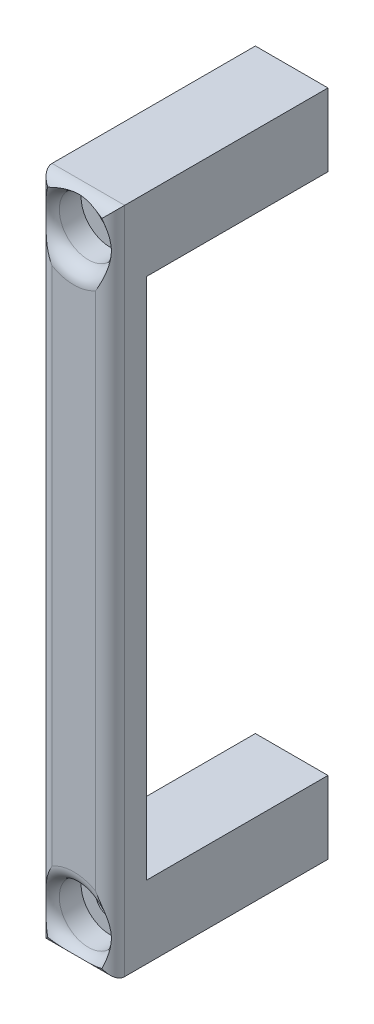
SolidWorks part; units mm, degrees
ref_plane "Piano frontale" through (0, 0, 0) normal (0, 0, 1) x (1, 0, 0)
ref_plane "Piano superiore" through (0, 0, 0) normal (0, 1, 0) x (1, 0, 0)
ref_plane "Piano destro" through (0, 0, 0) normal (1, 0, 0) x (0, 0, -1)
sketch "Schizzo1" plane through (0, 0, 0) normal (0, 0, 1) x (1, 0, 0)
  line L1 (-5, 5) -> (5, 5)
  line L2 (-5, 5) -> (-5, -5)
  line L3 (-5, -5) -> (5, -5)
  line L4 (5, 5) -> (5, -5)
  line L5 (-5, 5) -> (5, -5) construction
  line L6 (-5, -5) -> (5, 5) construction
  circle A0 centre (0, 0) radius 2
  point P0 (0, 0)
  dimension "D3" = 4
  dimension "D1" = 10
  dimension "D2" = 10
extrude "Estrusione-Estrusione1" add sketch "Schizzo1" along normal blind 25
sketch "Schizzo2" plane through (0, 0, 25) normal (0, 0, 1) x (1, 0, 0)
  line L0 (-5, -5) -> (5, -5)
  line L1 (-5, -5) -> (-5, 87)
  line L2 (5, -5) -> (5, 87)
  line L3 (-5, 87) -> (5, 87)
  line L4 (-5, 77) -> (5, 77) construction
  line L5 (5, 77) -> (5, 87) construction
  line L6 (0, 87) -> (0, 77) construction
  circle A0 centre (0, 82) radius 1.75
  circle A1 centre (0, 0) radius 2
  dimension "D3" = 3.5
  dimension "D1" = 92
  dimension "D2" = 10
extrude "Estrusione-Estrusione2" add sketch "Schizzo2" along normal blind 5
sketch "Schizzo3" plane through (0, 0, 25) normal (0, 0, -1) x (-1, 0, 0)
  line L1 (-5, 77) -> (5, 77)
  line L2 (-5, 77) -> (-5, 87)
  line L3 (-5, 87) -> (5, 87)
  line L4 (5, 77) -> (5, 87)
  line L5 (-5, 77) -> (5, 87) construction
  line L6 (-5, 87) -> (5, 77) construction
  circle A0 centre (0, 82) radius 1.75
  point P0 (0, 82)
  point P9 (0, 82)
extrude "Estrusione-Estrusione3" add sketch "Schizzo3" along normal blind 25
sketch "Schizzo4" plane through (0, 0, 30) normal (0, 0, 1) x (1, 0, 0)
  circle A0 centre (0, 0) radius 4
  circle A1 centre (0, 82) radius 4
  dimension "D1" = 8
extrude "Taglio-Estrusione1" cut sketch "Schizzo4" against normal blind 5
fillet "Raccordo1" radius 2 6 edges at (0, 87, 30) (5, 41, 30) (0, -5, 30) (-5, 41, 30) (4, 82, 30) (4, 0, 30)
